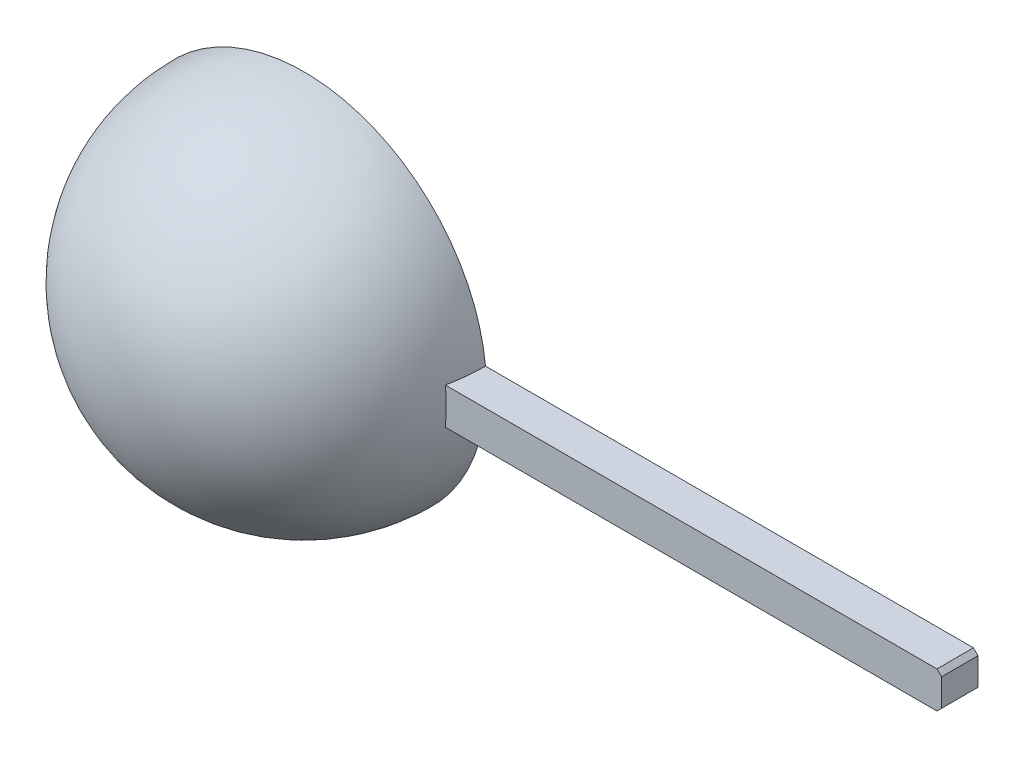
SolidWorks part; units mm, degrees
ref_plane "Plan de face" through (0, 0, 0) normal (0, 0, 1) x (1, 0, 0)
ref_plane "Plan de dessus" through (0, 0, 0) normal (0, 1, 0) x (1, 0, 0)
ref_plane "Plan de droite" through (0, 0, 0) normal (1, 0, 0) x (0, 0, -1)
sketch "Esquisse1" plane through (0, 0, 0) normal (0, 0, 1) x (1, 0, 0)
  line L0 (-40, 0) -> (40, 0)
  arc A0 (-40, 0) -> (40, 0) centre (0, 0) cw
  dimension "D1" = 40
revolve "Révolution1" add sketch "Esquisse1" angle 180 about L0
shell "Coque1" thickness 2 removed face at (-40, 0, 0)
sketch "Esquisse2" plane through (0, 0, 0) normal (0, 0, 1) x (1, 0, 0)
  line L0 (37.7889, 4) -> (147.7889, 4)
  line L1 (147.7889, 4) -> (147.7889, -4)
  line L2 (147.7889, -4) -> (37.7889, -4)
  line L3 (37.7889, -4) -> (37.7889, 4)
  circle A0 centre (0, 0) radius 38 construction
  dimension "D1" = 4
  dimension "D2" = 4
  dimension "D3" = 110
extrude "Boss.-Extru.1" add sketch "Esquisse2" along normal blind 8 contours L2 L3 L0 L1
chamfer "Chanfrein1" distance 1 angle 45 2 edges at (147.7889, 4, 4) (147.7889, -4, 4)
